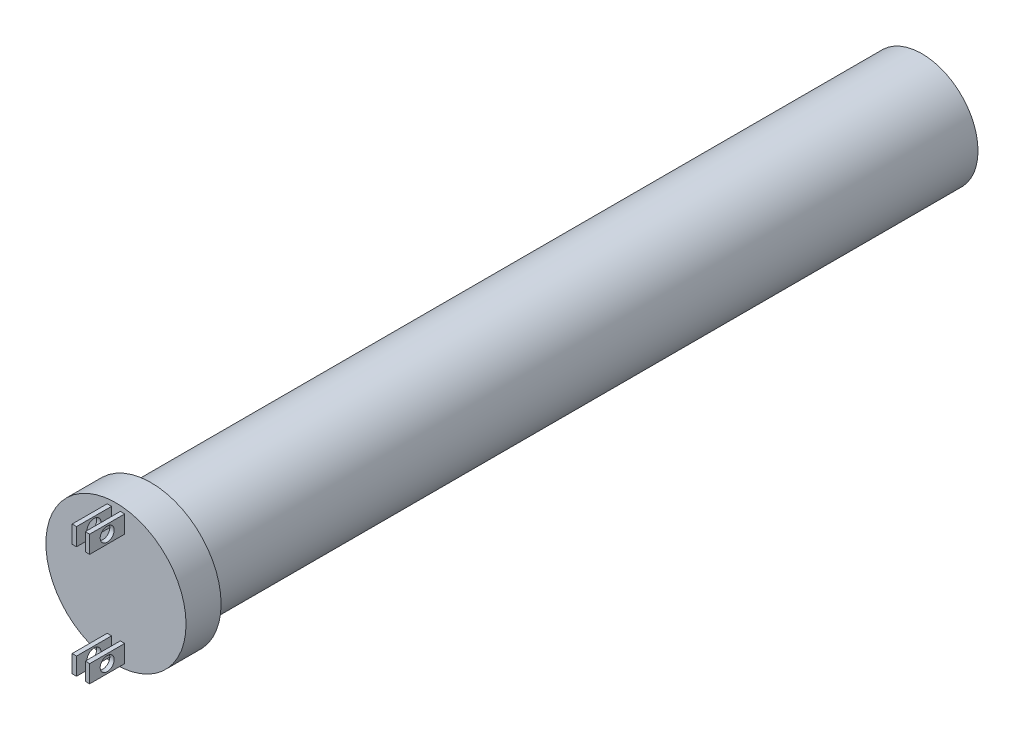
SolidWorks part; units mm, degrees
ref_plane "Front Plane" through (0, 0, 0) normal (0, 0, 1) x (1, 0, 0)
ref_plane "Top Plane" through (0, 0, 0) normal (0, 1, 0) x (1, 0, 0)
ref_plane "Right Plane" through (0, 0, 0) normal (1, 0, 0) x (0, 0, -1)
sketch "Sketch1" plane through (0, 0, 0) normal (0, 0, 1) x (1, 0, 0)
  circle A0 centre (0, 0) radius 20.32
  dimension "D1" = 40.64
extrude "Boss-Extrude1" add sketch "Sketch1" along normal blind 279.4
sketch "Sketch2" plane through (0, 0, 279.4) normal (0, 0, 1) x (1, 0, 0)
  circle A1 centre (0, 0) radius 25.4
extrude "Boss-Extrude2" add sketch "Sketch2" along normal blind 12.7
sketch "Sketch3" plane through (0, 0, 292.1) normal (0, 0, 1) x (1, 0, 0)
  line L0 (0, 0) -> (0, 20.32)
  line L1 (0, -55) -> (0, 55) construction
  line L2 (55, 0) -> (-55, 0) construction
  line L3 (-3.175, 17.145) -> (3.175, 17.145)
  line L4 (-3.175, 17.145) -> (-3.175, 23.495)
  line L5 (-3.175, 23.495) -> (3.175, 23.495)
  line L6 (3.175, 17.145) -> (3.175, 23.495)
  line L7 (-3.175, 17.145) -> (3.175, 23.495) construction
  line L8 (-3.175, 23.495) -> (3.175, 17.145) construction
  line L9 (-3.175, -17.145) -> (-3.175, -23.495)
  line L10 (-3.175, -17.145) -> (3.175, -17.145)
  line L11 (3.175, -17.145) -> (3.175, -23.495)
  line L12 (-3.175, -23.495) -> (3.175, -23.495)
  dimension "D1" = 20.32
  dimension "D2" = 6.35
  dimension "D3" = 6.35
extrude "Boss-Extrude3" add sketch "Sketch3" along normal blind 12.7 contours L9 L12 L11 L10 | L3 L6 L5 L4 region at (-3.0852, 20.32, 292.1) region at (0, -20.32, 292.1)
sketch "Sketch4" plane through (-3.175, 0, 0) normal (-1, 0, 0) x (0, 0, 1)
  line L0 (304.8, 17.145) -> (292.1, 23.495)
  line L1 (304.8, 23.495) -> (292.1, 17.145)
  line L2 (55, 0) -> (-55, 0) construction
  circle A0 centre (298.45, 20.32) radius 2.54
  circle A1 centre (298.45, -20.32) radius 2.54
  dimension "D1" = 5.08
extrude "Cut-Extrude1" cut sketch "Sketch4" against normal blind 6.35 contours A1 | A0 region at (-3.175, -20.32, 298.45)
sketch "Sketch5" plane through (3.175, 0, 0) normal (1, 0, 0) x (0, 0, -1)
  line L0 (-304.8, -23.495) -> (-304.8, -17.145)
  line L1 (-304.8, -17.145) -> (-292.1, -17.145)
  line L2 (-292.1, -17.145) -> (-292.1, -23.495)
  line L3 (-292.1, 25.4) -> (-292.1, -25.4) construction
  line L4 (-292.1, -17.145) -> (-292.1, -23.495) construction
  line L5 (-292.1, -23.495) -> (-304.8, -23.495)
extrude "Cut-Extrude2" cut sketch "Sketch5" against normal blind 3.175 from offset 1.5875 offset against normal yes
mirror "Mirror1" about plane through (0, 0, 0) normal (0, 1, 0) of "Cut-Extrude2"
